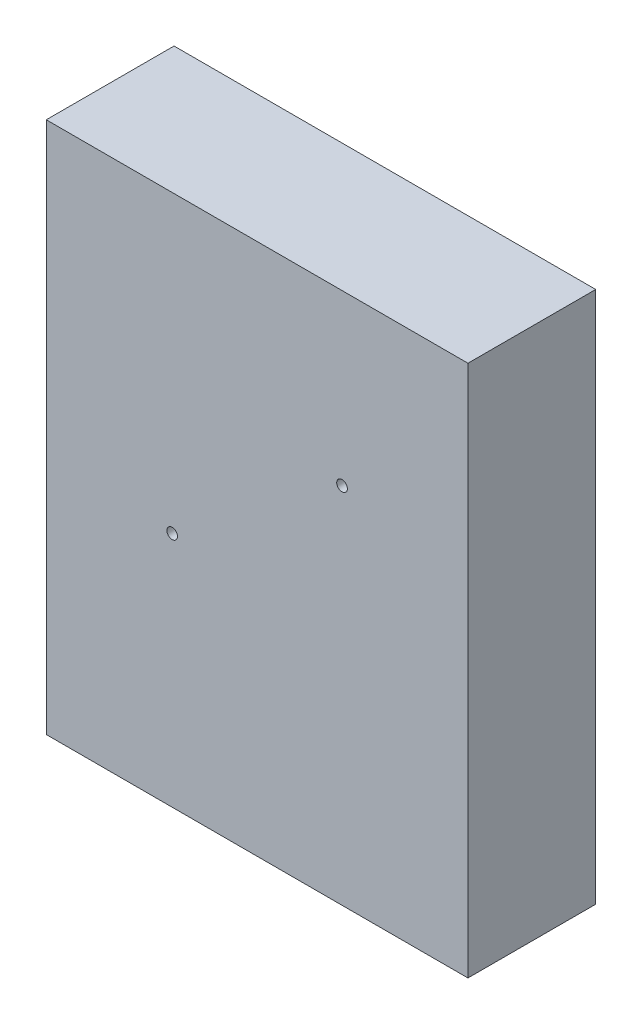
SolidWorks part; units mm, degrees
ref_plane "Front Plane" through (0, 0, 0) normal (0, 0, 1) x (1, 0, 0)
ref_plane "Top Plane" through (0, 0, 0) normal (0, 1, 0) x (1, 0, 0)
ref_plane "Right Plane" through (0, 0, 0) normal (1, 0, 0) x (0, 0, -1)
sketch "Sketch1" plane through (0, 0, 0) normal (0, 0, 1) x (1, 0, 0)
  line L1 (0, 0) -> (39.6, 0)
  line L2 (0, 0) -> (0, 50)
  line L3 (0, 50) -> (39.6, 50)
  line L4 (39.6, 0) -> (39.6, 50)
  dimension "D1" = 39.6
  dimension "D2" = 50
extrude "Boss-Extrude1" add sketch "Sketch1" along normal blind 12
sketch "Sketch2" plane through (0, 0, 12) normal (0, 0, 1) x (1, 0, 0)
  line L0 (39.6, 50) -> (0, 50) construction
  line L1 (0, 50) -> (0, 0) construction
  line L2 (39.6, 0) -> (39.6, 50) construction
  circle A0 centre (11.825, 22.27) radius 0.5
  circle A1 centre (27.775, 34.125) radius 0.5
  dimension "D1" = 1
  dimension "D2" = 27.73
  dimension "D3" = 11.825
  dimension "D4" = 15.875
  dimension "D5" = 11.825
extrude "Cut-Extrude1" cut sketch "Sketch2" against normal up to next
sketch "Sketch3" plane through (0, 0, 0) normal (0, -1, 0) x (1, 0, 0)
  line L0 (0, 6) -> (39.6, 6) construction
  line L1 (0, 12) -> (0, 0) construction
  line L2 (39.6, 12) -> (39.6, 0) construction
  circle A0 centre (5, 6) radius 0.5
  circle A1 centre (20, 6) radius 0.5
  dimension "D2" = 1
  dimension "D1" = 5
  dimension "D3" = 15
extrude "Cut-Extrude2" cut sketch "Sketch3" against normal blind 10
